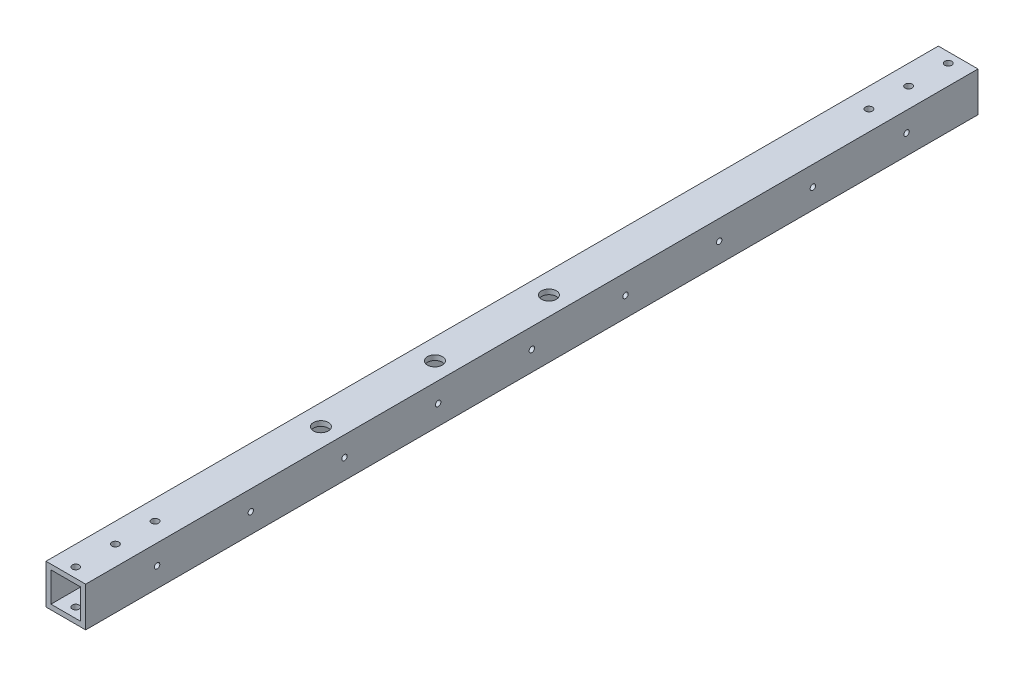
SolidWorks part; units mm, degrees
material "6061-T6 (SS)"
ref_plane "Front Plane" through (0, 0, 0) normal (0, 0, 1) x (1, 0, 0)
ref_plane "Top Plane" through (0, 0, 0) normal (0, 1, 0) x (1, 0, 0)
ref_plane "Right Plane" through (0, 0, 0) normal (1, 0, 0) x (0, 0, -1)
sketch "Sketch1" plane through (0, 0, 0) normal (0, 0, 1) x (1, 0, 0)
  line L1 (-12.7, -12.7) -> (12.7, -12.7)
  line L2 (-12.7, -12.7) -> (-12.7, 12.7)
  line L3 (-12.7, 12.7) -> (12.7, 12.7)
  line L4 (12.7, -12.7) -> (12.7, 12.7)
  line L5 (-12.7, -12.7) -> (12.7, 12.7) construction
  line L6 (-12.7, 12.7) -> (12.7, -12.7) construction
  point P0 (0, 0)
  dimension "D1" = 25.4
  dimension "D2" = 25.4
extrude "Extrude-Thin1" add sketch "Sketch1" along normal blind 571.5 thin thin type one direction reverse wall 3.175
hole_wizard "#8 Clearance Hole1" positions "3DSketch1" profile "Sketch3" hole size "#8" standard "ANSI Inch" end condition through all
sketch3d "3DSketch1"
  line L1 (12.7, 12.7, 0) -> (-12.7, 12.7, 0) construction
  line L6 (0, 12.7, 571.5) -> (0, 12.7, 0) construction
  line L7 (12.7, 12.7, 571.5) -> (-12.7, 12.7, 571.5) construction
  point P57 (0, 12.7, 6.35)
  point P59 (0, 12.7, 31.75)
  point P61 (0, 12.7, 57.15)
  point P63 (0, 12.7, 539.75)
  point P65 (0, 12.7, 514.35)
  point P67 (0, 12.7, 565.15)
  dimension "D1" = 25.4
  dimension "D2" = 25.4
  dimension "D3" = 6.35
  dimension "D4" = 25.4
  dimension "D5" = 25.4
  dimension "D6" = 6.35
sketch "Sketch3" plane through (0, 12.7, 565.15) normal (1, 0, 0) x (0, 0, 1)
  line L0 (0, 0) -> (0, 25.4)
  line L1 (0, 25.4) -> (2.2479, 25.4)
  line L2 (2.2479, 25.4) -> (2.2479, 0)
  line L5 (2.2479, 0) -> (0, 0)
  line L11 (0, -6.35) -> (0, 107.95) construction
  dimension "Thru Hole Dia." = 4.4958
  dimension "Thru Hole Depth" = 25.4
hole_wizard "#8-32 Tapped Hole1" positions "Sketch4" profile "Sketch5" tap size "#8-32" standard "ANSI Inch"
sketch "Sketch4" plane through (12.7, 82.55, 285.75) normal (1, 0, 0) x (0, 0, 1)
  point P0 (-300, 82.55)
  point P3 (-240, 82.55)
  point P6 (-180, 82.55)
  point P9 (-60, 82.55)
  point P12 (0, 82.55)
  point P15 (60, 82.55)
  point P18 (120, 82.55)
  point P21 (180, 82.55)
  point P24 (240, 82.55)
  point P27 (-120, 82.55)
  point P30 (-360, 82.55)
  point P33 (300, 82.55)
  point P36 (360, 82.55)
sketch "Sketch5" plane through (12.7, 0, -14.25) normal (0, 1, 0) x (0, 0, -1)
  line L0 (0, 0) -> (0, 11.7464)
  line L1 (0, 11.7464) -> (1.7272, 10.7086)
  line L2 (1.7272, 10.7086) -> (1.7272, 0)
  line L3 (1.7272, 0) -> (0, 0)
  line L4 (0, 11.7464) -> (-1.7272, 10.7086) construction
  line L5 (0, -6.35) -> (0, 107.95) construction
  dimension "Tap Drill Dia." = 3.4544
  dimension "Tap Drill Depth" = 10.7086
  dimension "Drill Angle" = 118
hole_wizard "3/8 (0.375) Diameter Hole2" positions "Sketch8" profile "Sketch9" hole size "3/8" standard "ANSI Inch" end condition through all
sketch "Sketch8" plane through (-346.075, -12.7, 285.75) normal (0, -1, 0) x (0, 0, 1)
  point P9 (-92.583, 346.075)
  point P12 (-35.433, 346.075)
  point P18 (35.814, 346.075)
  point P21 (92.964, 346.075)
  point P24 (-22.9616, -346.775)
  point P27 (50.0634, -346.775)
  point P30 (123.0884, -346.775)
  point P33 (-381, 114.3)
  point P36 (-381, 98.425)
  point P39 (-381, 82.55)
  point P42 (-381, -114.3)
  point P45 (-381, -130.175)
  point P48 (-381, -146.05)
sketch "Sketch9" plane through (-692.15, -12.7, 193.167) normal (1, 0, 0) x (0, 0, -1)
  line L0 (0, 0) -> (0, 25.4)
  line L1 (0, 25.4) -> (4.7625, 25.4)
  line L2 (4.7625, 25.4) -> (4.7625, 0)
  line L3 (4.7625, 0) -> (0, 0)
  line L4 (0, -6.35) -> (0, 107.95) construction
  dimension "Thru Hole Dia." = 9.525
  dimension "Thru Hole Depth" = 25.4
